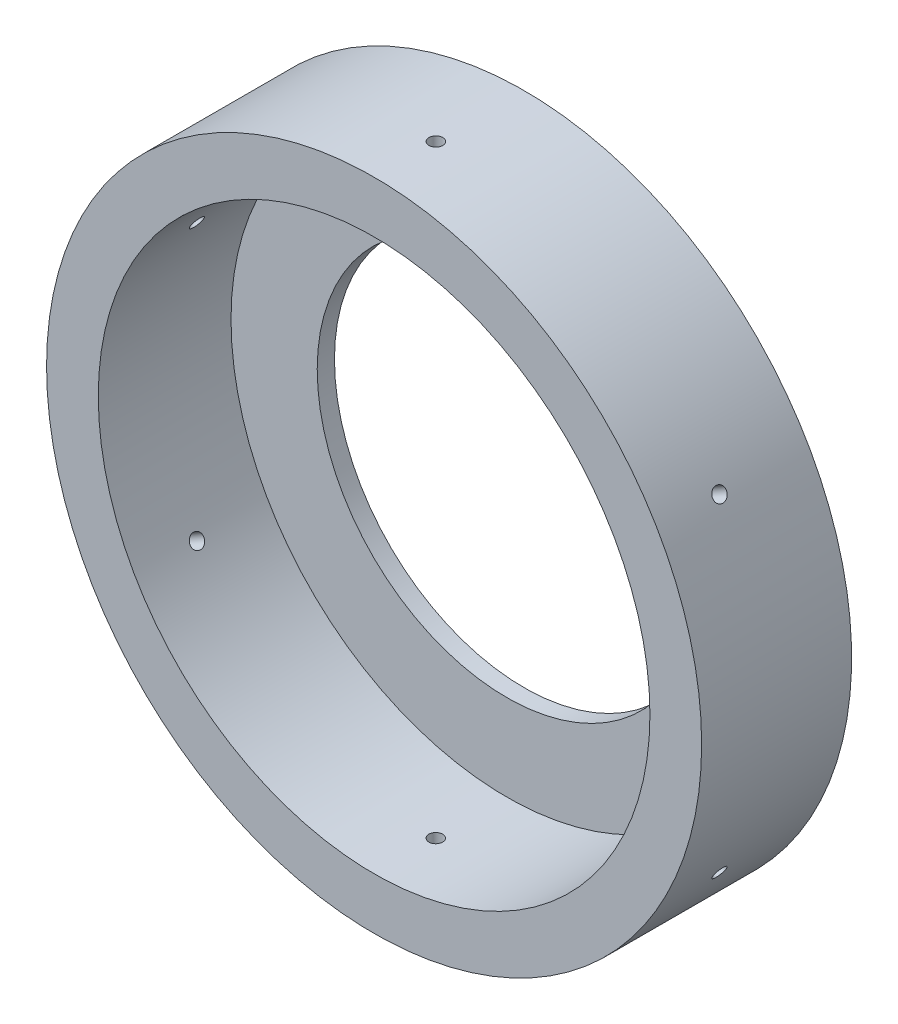
SolidWorks part; units mm, degrees
ref_plane "前视基准面" through (0, 0, 0) normal (0, 0, 1) x (1, 0, 0)
ref_plane "上视基准面" through (0, 0, 0) normal (0, 1, 0) x (1, 0, 0)
ref_plane "右视基准面" through (0, 0, 0) normal (1, 0, 0) x (0, 0, -1)
sketch "草图1" plane through (0, 0, 0) normal (0, 0, 1) x (1, 0, 0)
  circle A0 centre (0, 0) radius 55
  circle A1 centre (0, 0) radius 95
extrude "凸台-拉伸1" add sketch "草图1" along normal blind 5 contours A1 A0 region at (-92.313, 0, 0)
sketch "草图2" plane through (0, 0, 0) normal (0, 0, 1) x (1, 0, 0)
  circle A0 centre (0, 0) radius 95
  circle A1 centre (0, 0) radius 80
extrude "凸台-拉伸2" add sketch "草图2" along normal blind 38.5 contours A0 A1 region at (-92.313, 0, 0)
sketch "草图3" plane through (0, 0, 0) normal (0, 1, 0) x (1, 0, 0)
  circle A0 centre (0, -20.6) radius 2
  dimension "D1" = 20.6
extrude "切除-拉伸2" cut sketch "草图3" against normal blind 100
pattern_circular "阵列(圆周)2" count 6 over 360 about axis through (0, 0, 5) along (0, 0, -1) of "切除-拉伸2" reverse direction yes
sketch "草图5" plane through (0, 0, 0) normal (0, 0, -1) x (-1, 0, 0)
  circle A0 centre (0, 0) radius 80
extrude "切除-拉伸3" cut sketch "草图5" against normal blind 20
sketch "草图6" plane through (0, 0, 0) normal (0, 0, -1) x (-1, 0, 0)
  circle A0 centre (0, 0) radius 95
  circle A1 centre (0, 0) radius 55
extrude "凸台-拉伸3" add sketch "草图6" along normal blind 5
